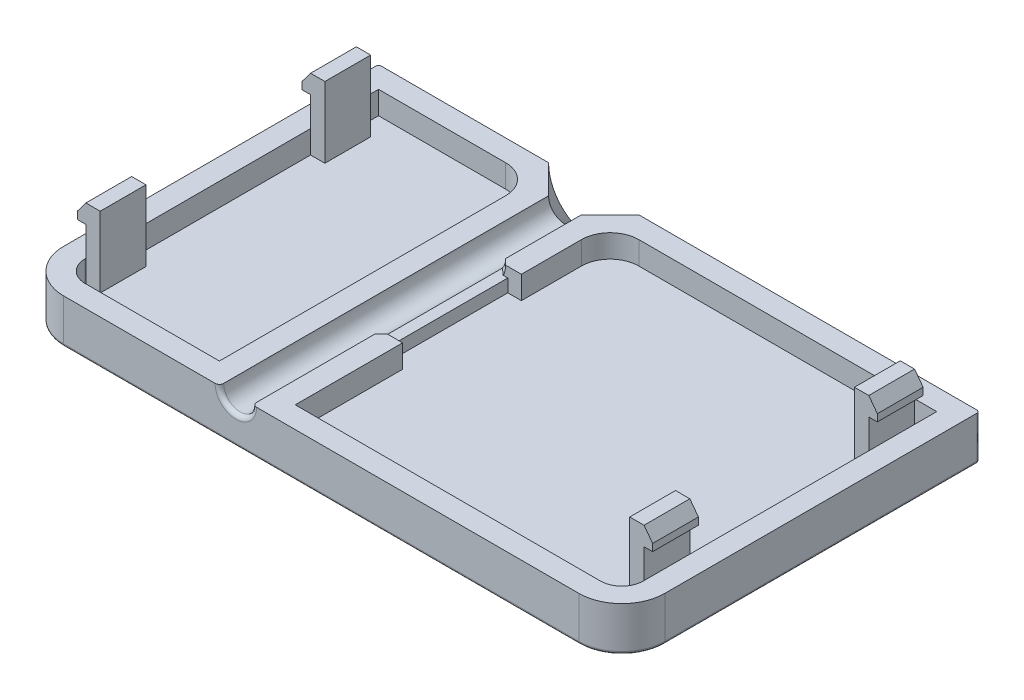
SolidWorks part; units mm, degrees
ref_plane "前视基准面" through (0, 0, 0) normal (0, 0, 1) x (1, 0, 0)
ref_plane "上视基准面" through (0, 0, 0) normal (0, 1, 0) x (1, 0, 0)
ref_plane "右视基准面" through (0, 0, 0) normal (1, 0, 0) x (0, 0, -1)
sketch "草图1" plane through (0, 0, 0) normal (0, 1, 0) x (1, 0, 0)
  line L0 (-102.0821, 0) -> (151.6587, 0) construction
  line L1 (0, 100.0802) -> (0, -103.8775) construction
  line L2 (-21, -12.5) -> (-21, 12.5)
  line L3 (-21, 12.5) -> (21, 12.5)
  line L4 (21, 12.5) -> (21, -12.5)
  line L5 (21, -12.5) -> (-21, -12.5)
  dimension "D1" = 25
  dimension "D2" = 42
extrude "凸台-拉伸1" add sketch "草图1" along normal blind 3.1
sketch "草图3" plane through (0, 0, 12.5) normal (0, 0, 1) x (1, 0, 0)
  line L0 (-21, 3.1) -> (21, 3.1) construction
  line L2 (-21, 3.1) -> (-21, 0) construction
  circle A0 centre (-5.97, 3.1) radius 1.15
  dimension "D1" = 2.3
  dimension "D2" = 15.03
extrude "切除-拉伸1" cut sketch "草图3" against normal through all
sketch "草图5" plane through (0, 3.1, 0) normal (0, 1, 0) x (1, 0, 0)
  line L0 (-4.27, 4.8) -> (-4.27, -3.5)
  line L2 (-4.27, -3.5) -> (11.43, -3.5)
  line L3 (11.43, -3.5) -> (11.43, 4.8)
  line L4 (11.43, 4.8) -> (-4.27, 4.8)
  line L5 (-4.82, 12.5) -> (-4.82, -12.5) construction
  line L11 (-4.82, -12.5) -> (21, -12.5) construction
  line L12 (21, 12.5) -> (-4.82, 12.5) construction
  dimension "D1" = 7.7
  dimension "D2" = 9
  dimension "D3" = 0.55
  dimension "D4" = 15.7
extrude "切除-拉伸3" cut sketch "草图5" against normal blind 1.6
fillet "圆角4" radius 3 2 edges at (-21, 1.55, 12.5) (21, 1.55, 12.5)
sketch "草图10" plane through (0, 3.1, 0) normal (0, 1, 0) x (1, 0, 0)
  line L0 (-4.27, -3.5) -> (-5.5941, -3.5)
  line L1 (-5.5941, -3.5) -> (-5.5941, 4.8)
  line L2 (-5.5941, 4.8) -> (-4.27, 4.8)
  line L3 (-4.27, 4.8) -> (-4.27, -3.5)
  dimension "D1" = 1.3241
extrude "切除-拉伸4" cut sketch "草图10" against normal blind 0.7
sketch "草图11" plane through (0, 3.1, 0) normal (0, 1, 0) x (1, 0, 0)
  line L0 (-3.32, -11) -> (-3.32, 11)
  line L2 (-3.32, 11) -> (19.5, 11)
  line L3 (19.5, 11) -> (19.5, -9.5)
  line L4 (18, -11) -> (-3.32, -11)
  line L5 (-19.5, 11) -> (-8.62, 11)
  line L7 (-8.62, 11) -> (-8.62, -11)
  line L8 (-8.62, -11) -> (-18, -11)
  line L9 (-19.5, -9.5) -> (-19.5, 11)
  line L11 (-7.12, 12.5) -> (-21, 12.5) construction
  line L12 (-21, 12.5) -> (-21, -9.5) construction
  line L13 (21, -9.5) -> (21, 12.5) construction
  line L15 (-4.82, -12.5) -> (18, -12.5) construction
  line L16 (-7.12, -12.5) -> (-7.12, 12.5) construction
  line L17 (-4.82, 12.5) -> (-4.82, 4.8) construction
  arc A1 (19.5, -9.5) -> (18, -11) centre (18, -9.5) cw
  arc A2 (-18, -11) -> (-19.5, -9.5) centre (-18, -9.5) cw
  dimension "D7" = 1.5
  dimension "D1" = 1.5
  dimension "D2" = 1.5
  dimension "D3" = 1.5
  dimension "D4" = 1.5
  dimension "D5" = 1.5
  dimension "D6" = 1.5
extrude "切除-拉伸5" cut sketch "草图11" against normal up to surface (1.6 mm away) up to face at (3.58, 1.5, -0.65)
fillet "圆角5" radius 0.3 1 edges at (-5.97, 1.95, 12.5)
chamfer "倒角1" distance 0.4 angle 45 2 edges at (-4.881, 2.7304, -4.8) (-4.881, 2.7304, 3.5)
chamfer "倒角2" distance 2 distance2 2 1 edges at (-5.97, 1.95, -12.5)
fillet "圆角6" radius 2 2 edges at (-3.32, 2.3, -11) (-8.62, 2.3, -11)
sketch "草图13" plane through (0, 1.5, 0) normal (0, -1, 0) x (1, 0, 0)
  line L0 (19.5, 9.45) -> (19.5, 6.25)
  line L1 (19.5, 6.25) -> (18.5, 6.25)
  line L2 (18.5, 6.25) -> (18.5, 9.45)
  line L3 (18.5, 9.45) -> (19.5, 9.45)
  line L4 (19.5, -6.25) -> (18.5, -6.25)
  line L5 (18.5, -6.25) -> (18.5, -9.45)
  line L6 (18.5, -9.45) -> (19.5, -9.45)
  line L7 (19.5, -9.45) -> (19.5, -6.25)
  line L8 (19.5, -11) -> (19.5, 9.5) construction
  line L9 (39.6338, 0) -> (-46.3581, 0) construction
  line L12 (0, 35.0751) -> (0, -38.0819) construction
  line L13 (-19.5, -11) -> (-19.5, 9.5) construction
  line L14 (-19.5, -9.45) -> (-19.5, -6.25)
  line L15 (-18.5, -9.45) -> (-19.5, -9.45)
  line L16 (-18.5, -6.25) -> (-18.5, -9.45)
  line L17 (-19.5, -6.25) -> (-18.5, -6.25)
  line L18 (-18.5, 9.45) -> (-19.5, 9.45)
  line L19 (-18.5, 6.25) -> (-18.5, 9.45)
  line L20 (-19.5, 6.25) -> (-18.5, 6.25)
  line L21 (-19.5, 9.45) -> (-19.5, 6.25)
  dimension "D1" = 12.5
  dimension "D2" = 3.2
  dimension "D3" = 3.2
  dimension "D4" = 1
  dimension "D5" = 1
extrude "凸台-拉伸2" add sketch "草图13" against normal blind 4.95
sketch "草图14" plane through (0, 0, -9.45) normal (0, 0, -1) x (-1, 0, 0)
  line L0 (-19.5, 6.45) -> (-19.5, 5.15)
  line L1 (-19.5, 5.15) -> (-20.1, 5.15)
  line L2 (-20.1, 5.15) -> (-20.1, 5.65)
  line L3 (-20.1, 5.65) -> (-19.5, 6.45)
  line L5 (0, 23.4365) -> (0, -14.762) construction
  line L6 (20.1, 5.65) -> (19.5, 6.45)
  line L7 (20.1, 5.15) -> (20.1, 5.65)
  line L8 (19.5, 5.15) -> (20.1, 5.15)
  line L9 (19.5, 6.45) -> (19.5, 5.15)
  dimension "D1" = 1.3
  dimension "D2" = 0.5
  dimension "D3" = 0.6
extrude "凸台-拉伸3" add sketch "草图14" against normal blind 3.2
mirror "镜向1" about plane through (0, 0, 0) normal (0, 0, 1) of "凸台-拉伸3"
fillet "圆角7" radius 0.2 2 edges at (21, 1.55, -12.5) (-21, 1.55, -12.5)
fillet "圆角8" radius 0.2 8 edges at (-20.9414, 0, -12.4414) (-21, 0, -1.4) (-20.1213, 0, 11.6213) (0, 0, 12.5) (20.1213, 0, 11.6213) (21, 0, -1.4) (20.9414, 0, -12.4414) (7.6945, 0, -12.5)
